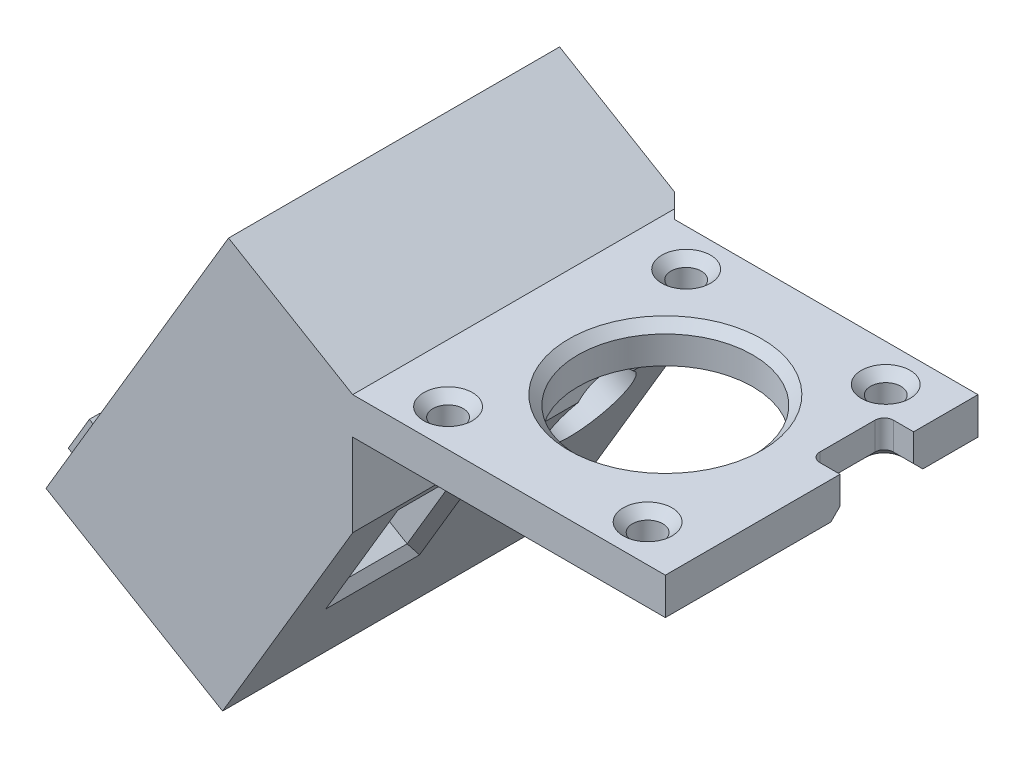
SolidWorks part; units mm, degrees
ref_plane "Front Plane" through (0, 0, 0) normal (0, 0, 1) x (1, 0, 0)
ref_plane "Top Plane" through (0, 0, 0) normal (0, 1, 0) x (1, 0, 0)
ref_plane "Right Plane" through (0, 0, 0) normal (1, 0, 0) x (0, 0, -1)
sketch "Sketch1" plane through (0, 0, 0) normal (0, 0, 1) x (1, 0, 0)
  line L0 (0, 0) -> (17, 0)
  line L1 (17, 0) -> (17, 4)
  line L2 (17, 4) -> (-17, 4)
  line L4 (-17, 0) -> (0, 0)
  line L5 (0, 0) -> (0, 4) construction
  line L6 (-30.5, 12) -> (-17, 4)
  line L7 (-17, 0) -> (-17, -9)
  line L8 (-17, -9) -> (-22.3529, -18.0331)
  line L9 (-17, 4) -> (-17, 12) construction
  line L10 (-17, 12) -> (-30.5, 12) construction
  line L11 (-30.5, 12) -> (-17, 4)
  line L12 (-40.1017, 1.4428) -> (-2.401, -20.8984) construction
  line L13 (-30.5, 12) -> (-32.2727, 9.0085)
  line L14 (-32.2727, 9.0085) -> (-30.122, 7.734)
  line L15 (-30.122, 7.734) -> (-32.773, 3.2605)
  line L16 (-32.773, 3.2605) -> (-25.0304, -1.3277)
  line L17 (-25.0304, -1.3277) -> (-26.5088, -3.8226) construction
  line L18 (-26.5088, -3.8226) -> (-22.6364, -6.1173) construction
  line L19 (-22.6364, -6.1173) -> (-25.0835, -10.2467) construction
  line L20 (-28.9558, -7.952) -> (-25.0835, -10.2467) construction
  line L21 (-28.9558, -7.952) -> (-32.2695, -13.5439) construction
  line L22 (-32.2695, -13.5439) -> (-35.8828, -11.4027)
  line L23 (-35.8828, -11.4027) -> (-40.0122, -18.3711)
  line L24 (-40.0122, -18.3711) -> (-44.1416, -15.924)
  line L25 (-44.1416, -15.924) -> (-46.7925, -20.3975)
  line L26 (-46.7925, -20.3975) -> (-48.9433, -19.123)
  line L27 (-32.773, 3.2605) -> (-44.1416, -15.924) construction
  line L28 (-32.2695, -13.5439) -> (-29.8843, -9.5188)
  line L29 (-29.8843, -9.5188) -> (-25.0304, -1.3277)
  line L30 (-48.9433, -19.123) -> (-50.3528, -21.5016)
  line L31 (-22.3529, -18.0331) -> (-31.1513, -32.8803)
  line L32 (-31.1513, -32.8803) -> (-50.3528, -21.5016)
  point P8 (0, 4)
  point P23 (-23.8599, -8.182)
  dimension "D1" = 34
  dimension "D2" = 10.5
  dimension "D3" = 9
  dimension "D4" = 2.4
  dimension "D5" = 13.5
  dimension "D6" = 8
  dimension "D7" = 4
  dimension "D8" = 2.5
  dimension "D9" = 5.2
  dimension "D10" = 9
  dimension "D11" = 2.9
  dimension "D12" = 6.5
  dimension "D13" = 4.2
  dimension "D14" = 8.1
  dimension "D15" = 5.2
  dimension "D16" = 2.5
extrude "Boss-Extrude1" add sketch "Sketch1" along normal blind 13 contours L32 L31 L8 L7 L4 L0 L1 L2 L6 L13 L14 L15 L16 L29 L28 L22 L23 L24 L25 L26 L30 region at (-24.0239, -9.8576, 0)
sketch "Sketch2" plane through (0, 0, 0) normal (0, 0, -1) x (-1, 0, 0)
  line L0 (30.5, 12) -> (50.3528, -21.5016)
  line L1 (50.3528, -21.5016) -> (31.1513, -32.8803)
  line L2 (31.1513, -32.8803) -> (17, -9)
  line L3 (17, -9) -> (17, 0)
  line L4 (17, 0) -> (17, 4)
  line L5 (17, 4) -> (30.5, 12)
extrude "Boss-Extrude2" add sketch "Sketch2" along normal blind 2
sketch "Sketch3" plane through (0, 0, 13) normal (0, 0, 1) x (1, 0, 0)
  line L0 (-30.5, 12) -> (-17, 4)
  line L1 (-17, 4) -> (17, 4)
  line L2 (17, 4) -> (17, 0)
  line L3 (17, 0) -> (-17, 0)
  line L4 (-17, 0) -> (-17, -9)
  line L5 (-17, -9) -> (-31.1513, -32.8803)
  line L6 (-31.1513, -32.8803) -> (-50.3528, -21.5016)
  line L7 (-31.1513, -32.8803) -> (-50.3528, -21.5016) construction
  line L8 (-50.3528, -21.5016) -> (-30.5, 12)
extrude "Boss-Extrude3" add sketch "Sketch3" along normal blind 21
sketch "Sketch4" plane through (-17.9427, 10.6327, 0) normal (-0.8603, 0.5098, 0) x (0, 0, 1)
  line L0 (6.5, -13.9028) -> (6.5, -28.1028) construction
  line L1 (13, -13.9028) -> (0, -13.9028) construction
  line L2 (13, -28.1028) -> (0, -28.1028) construction
  line L3 (6.5, -13.9028) -> (6.5, -19.7778) construction
  circle A0 centre (6.5, -19.7778) radius 4.5
extrude "Cut-Extrude1" cut sketch "Sketch4" against normal blind 21
ref_plane "Plane1" through (-23.5346, 13.9464, 0) normal (-0.8603, 0.5098, 0) x (0, 0, 1)
sketch "Sketch6" plane through (-23.5346, 13.9464, 0) normal (-0.8603, 0.5098, 0) x (0, 0, 1)
  line L0 (13, -25.0528) -> (34, -25.0528) construction
  line L1 (19.4, -31.7528) -> (27.6, -31.7528)
  line L2 (19.4, -31.7528) -> (19.4, -18.3528)
  line L3 (19.4, -18.3528) -> (27.6, -18.3528)
  line L4 (27.6, -31.7528) -> (27.6, -18.3528)
  line L5 (13, -8.7028) -> (13, -41.4028) construction
  line L6 (34, -5.2255) -> (34, -44.1676) construction
  line L7 (23.5, -18.3528) -> (23.5, -25.0528) construction
  point P10 (19.4, -25.0528)
  point P13 (0, 0)
  point P14 (23.5, -25.0528)
  dimension "D1" = 8.2
  dimension "D2" = 13.4
extrude "Cut-Extrude2" cut sketch "Sketch6" against normal blind 21
sketch "Sketch7" plane through (-23.5346, 13.9464, 0) normal (0.8603, -0.5098, 0) x (0, 0, -1)
  line L0 (-27.6, -25.0528) -> (-19.4, -25.0528) construction
  line L1 (-27.6, -18.3528) -> (-27.6, -31.7528) construction
  line L2 (-19.4, -18.3528) -> (-19.4, -31.7528) construction
  circle A0 centre (-23.5, -25.0528) radius 3
extrude "Cut-Extrude3" cut sketch "Sketch7" against normal blind 21
chamfer "Chamfer1" distance 1 angle 45 5 edges at (-34.7771, -5.0254, 23.5) (-24.8222, -22.1999, 23.5) (-21.4065, -16.4359, 27.6) (-17.9908, -10.672, 23.5) (-21.4065, -16.4359, 19.4)
sketch "Sketch8" plane through (-27.836, 16.4954, 0) normal (-0.8603, 0.5098, 0) x (0, 0, 1)
  text T0 "KILL\r\n" font "Impact" height 4.5
extrude "Boss-Extrude4" add sketch "Sketch8" along normal blind 1
sketch "Sketch9" plane through (-27.836, 16.4954, 0) normal (-0.8603, 0.5098, 0) x (0, 0, 1)
  text T0 "SWITCH\r\n" font "Impact" height 4.5
extrude "Boss-Extrude5" add sketch "Sketch9" along normal blind 1
sketch "Sketch11" plane through (0, 4, 0) normal (0, 1, 0) x (1, 0, 0)
  line L0 (0, 0) -> (0, -34) construction
  line L1 (17, -34) -> (-17, -34) construction
  line L2 (17, -17) -> (-17, -17) construction
  line L3 (17, -34) -> (17, 0) construction
  line L4 (-17, -34) -> (-17, 0) construction
  line L5 (-12.3314, -4.0543) -> (12.6686, -4.0543) construction
  line L7 (17, 0) -> (17, -7) construction
  line L8 (17, -7) -> (14.8, -7)
  line L9 (13.8, -8) -> (13.8, -14)
  line L10 (14.8, -15) -> (17, -15)
  line L11 (17, -15) -> (17, -7)
  circle A0 centre (0, -17) radius 9.5
  circle A1 centre (0, -17) radius 17 construction
  circle A2 centre (-10.6814, -4.0543) radius 1.65
  circle A3 centre (11.0186, -4.0543) radius 1.65
  circle A4 centre (-10.6814, -29.9457) radius 1.65
  circle A5 centre (11.0186, -29.9457) radius 1.65
  arc A6 (13.8, -14) -> (14.8, -15) centre (14.8, -14) ccw
  arc A7 (13.8, -8) -> (14.8, -7) centre (14.8, -8) cw
  point P32 (13.8, -15)
  point P35 (13.8, -7)
  dimension "D1" = 25
  dimension "D2" = 34
  dimension "D6" = 1
  dimension "D3" = 7
  dimension "D4" = 3.2
  dimension "D5" = 8
extrude "Cut-Extrude4" cut sketch "Sketch11" against normal blind 11
chamfer "Chamfer2" distance 1 angle 45 10 edges at (15.9, 0, 15) (14.0929, 0, 14.7071) (13.8, 0, 11) (14.0929, 0, 7.2929) (15.9, 0, 7) (-9.5, 4, 17) (-9.0314, 4, 29.9457) (12.6686, 4, 29.9457) (9.3686, 4, 4.0543) (-12.3314, 4, 4.0543)
sketch "Sketch12" plane through (-25.6853, 15.2209, 0) normal (-0.8603, 0.5098, 0) x (0, 0, 1)
  line L0 (6.5, -8.7028) -> (6.5, -41.4028) construction
  line L1 (13, -8.7028) -> (0, -8.7028) construction
  line L2 (13, -41.4028) -> (0, -41.4028) construction
  line L3 (13, -11.2028) -> (0, -11.2028) construction
  line L4 (13, -8.7028) -> (13, -41.4028) construction
  line L5 (0, -41.4028) -> (0, -8.7028) construction
  line L6 (13, -8.7028) -> (0, -8.7028) construction
  line L7 (0, -25.0528) -> (13, -25.0528) construction
  circle A0 centre (6.5, -11.2028) radius 1.25
  circle A1 centre (6.5, -38.9028) radius 1.25
  dimension "D1" = 2.5
extrude "Cut-Extrude5" cut sketch "Sketch12" against normal blind 11
chamfer "Chamfer3" distance 1 angle 45 2 edges at (-17, -2.5, -2) (-17, 2, 0)
